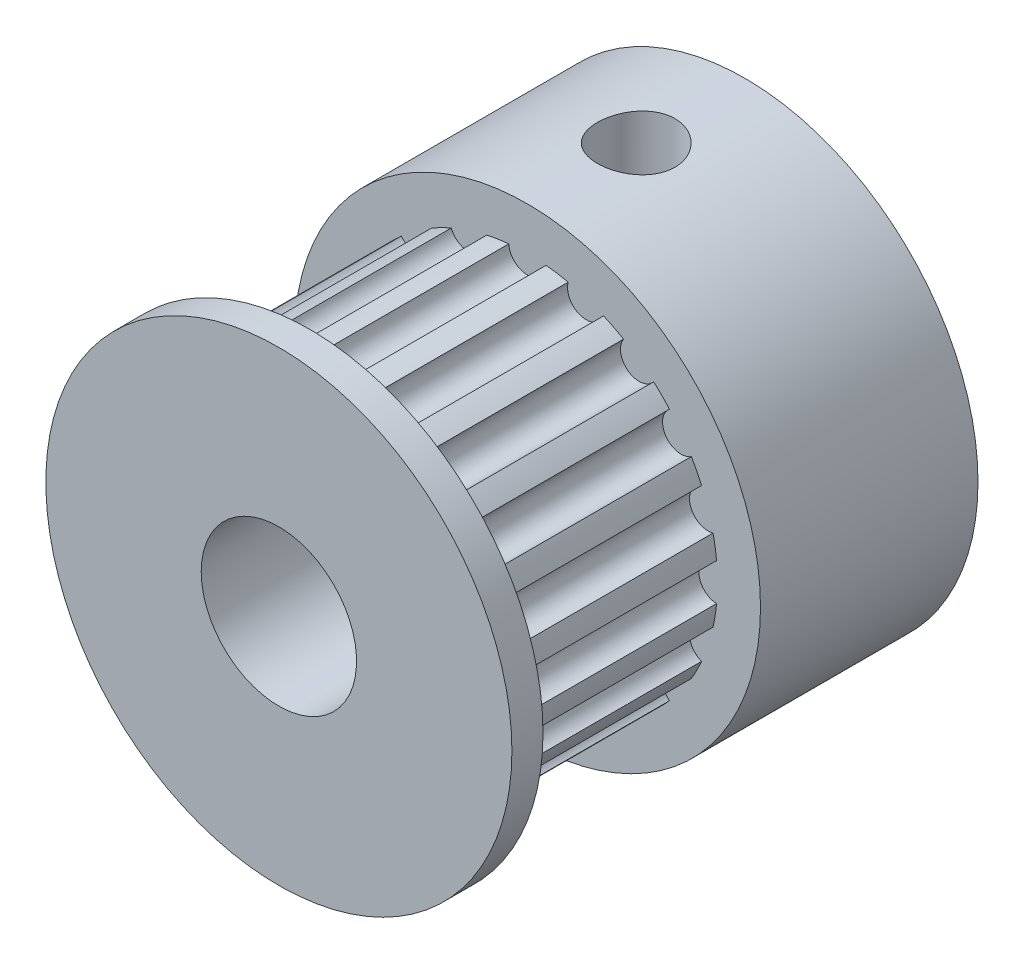
SolidWorks part; units mm, degrees
material "6061 合金"
ref_plane "前基準面" through (0, 0, 0) normal (0, 0, 1) x (1, 0, 0)
ref_plane "上基準面" through (0, 0, 0) normal (0, 1, 0) x (1, 0, 0)
ref_plane "右基準面" through (0, 0, 0) normal (1, 0, 0) x (0, 0, -1)
sketch "草圖1" plane through (0, 0, 0) normal (0, 0, 1) x (1, 0, 0)
  circle A0 centre (0, 0) radius 7.5
  dimension "D1" = 15
extrude "填料-伸長1" add sketch "草圖1" along normal mid plane 7
sketch "草圖2" plane through (0, 0, 3.5) normal (0, 0, 1) x (1, 0, 0)
  circle A0 centre (0, 0) radius 6.115
  dimension "D1" = 12.23
extrude "填料-伸長2" add sketch "草圖2" along normal blind 7
sketch "草圖7" plane through (0, 0, 10.5) normal (0, 0, 1) x (1, 0, 0)
  line L0 (0, 0) -> (0, 6.115) construction
  arc A0 (-0.5993, 6.0856) -> (0.5993, 6.0856) centre (0, 6.115) ccw
  circle A1 centre (0, 0) radius 6.115 construction
  circle A2 centre (0, 0) radius 6.115 construction
  arc A3 (-0.5993, 6.0856) -> (0.5993, 6.0856) centre (0, 0) cw
  point P10 (0, 5.515)
  dimension "D1" = 0.6
extrude "除料-伸長3" cut sketch "草圖7" against normal up to surface (7 mm away) up to face at (6.115, 0, 3.5)
sketch "草圖3" plane through (0, 0, 10.5) normal (0, 0, 1) x (1, 0, 0)
  circle A0 centre (0, 0) radius 7.5
  circle A1 centre (0, 0) radius 7.5 construction
extrude "填料-伸長3" add sketch "草圖3" along normal blind 1
sketch "草圖6" plane through (0, 0, -3.5) normal (0, 0, -1) x (-1, 0, 0)
  circle A0 centre (0, 0) radius 2.5
  dimension "D1" = 5
extrude "除料-伸長2" cut sketch "草圖6" against normal through all
pattern_circular "環狀複製排列2" count 20 over 360 about axis through (0, 0, 10.5) along (0, 0, -1) of "除料-伸長3"
hole_wizard "M3x0.5 螺紋孔3" positions "草圖12" profile "草圖13" tap size "M3x0.5" standard "Ansi Metric" end condition through all
sketch "草圖12" plane through (0, 0, 0) normal (0, 1, 0) x (1, 0, 0)
  point P0 (0, 0)
sketch "草圖13" plane through (0, 0, 0) normal (1, 0, 0) x (0, 0, -1)
  line L0 (0, 0) -> (0, 7.5)
  line L1 (0, 7.5) -> (1.25, 7.5)
  line L2 (1.25, 7.5) -> (1.25, 0)
  line L5 (1.25, 0) -> (0, 0)
  line L11 (0, -6.35) -> (0, 107.95) construction
  dimension "貫穿螺孔鑽直徑" = 2.5
  dimension "貫穿螺孔鑽深度" = 7.5
pattern_circular "環狀複製排列4" count 2 over 90 about axis through (0, 0, 3.5) along (0, 0, -1) of "M3x0.5 螺紋孔3" reverse direction yes
